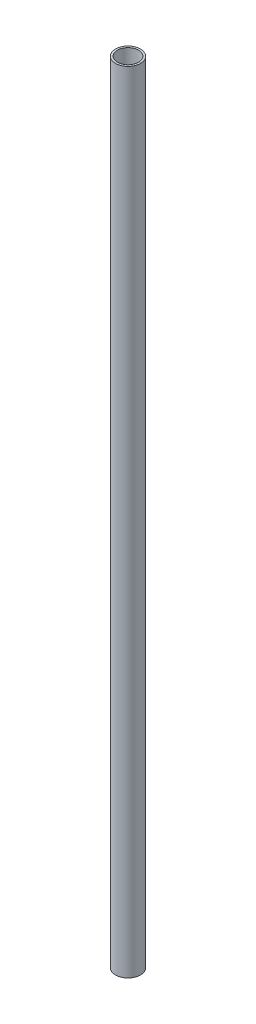
SolidWorks part; units mm, degrees
material "AISI 4130 Steel, annealed at 865C"
ref_plane "Front Plane" through (0, 0, 0) normal (0, 0, 1) x (1, 0, 0)
ref_plane "Top Plane" through (0, 0, 0) normal (0, 1, 0) x (1, 0, 0)
ref_plane "Right Plane" through (0, 0, 0) normal (1, 0, 0) x (0, 0, -1)
sketch "Sketch1" plane through (0, 0, 0) normal (0, 1, 0) x (1, 0, 0)
  circle A0 centre (0, 0) radius 6.6929
  circle A1 centre (0, 0) radius 7.9375
  dimension "D1" = 15.875
  dimension "D2" = 13.3858
extrude "Boss-Extrude1" add sketch "Sketch1" along normal blind 501.65
ref_axis "Axis1" through (0, 501.65, 0) along (0, -1, 0)
